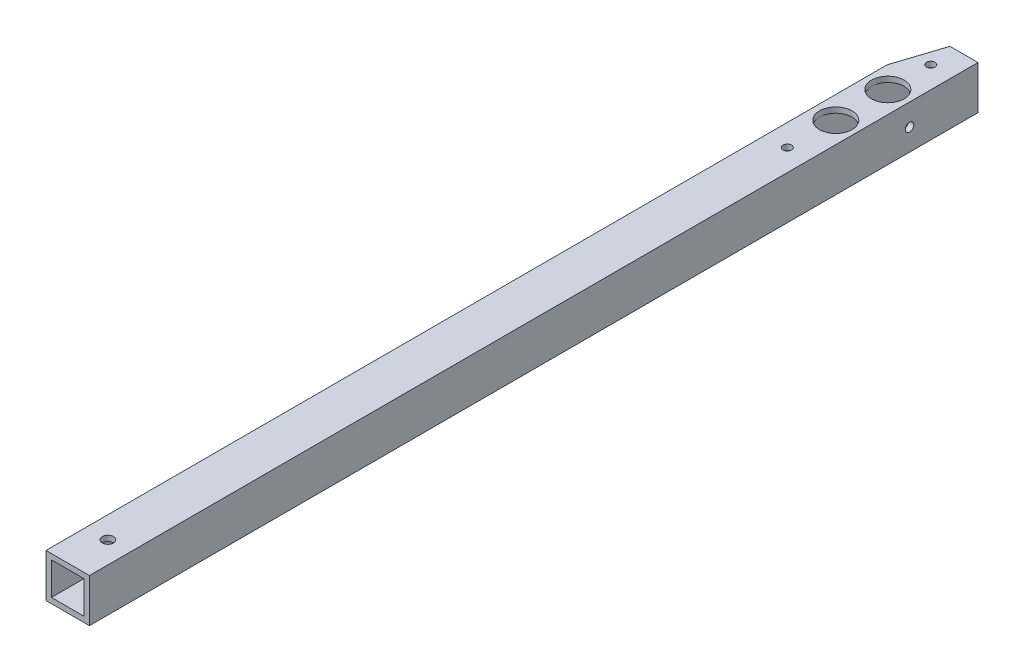
SolidWorks part; units mm, degrees
ref_plane "Front Plane" through (0, 0, 0) normal (0, 0, 1) x (1, 0, 0)
ref_plane "Top Plane" through (0, 0, 0) normal (0, 1, 0) x (1, 0, 0)
ref_plane "Right Plane" through (0, 0, 0) normal (1, 0, 0) x (0, 0, -1)
sketch "Sketch1" plane through (0, 0, 0) normal (0, 0, 1) x (1, 0, 0)
  line L0 (-9.525, 9.525) -> (9.525, 9.525)
  line L2 (-12.7, 12.7) -> (12.7, 12.7)
  line L3 (-12.7, 12.7) -> (-12.7, -12.7)
  line L4 (-12.7, -12.7) -> (12.7, -12.7)
  line L5 (12.7, 12.7) -> (12.7, -12.7)
  line L10 (9.525, 9.525) -> (9.525, -9.525)
  line L11 (-9.525, -9.525) -> (9.525, -9.525)
  line L12 (-9.525, 9.525) -> (-9.525, -9.525)
  point P12 (0, 12.7)
  point P14 (12.7, 0)
  dimension "Wall Thickness" = 3.175
  dimension "Outside Width" = 25.4
  dimension "Outside Height" = 25.4
  dimension "Inside Height" = 19.05
  dimension "Inside Width" = 19.05
sketch "Sketch2" plane through (0, 0, 0) normal (1, 0, 0) x (0, 0, -1)
  line L0 (266.7, 0) -> (-266.7, 0)
  point P4 (0, 0)
  point P7 (-266.7, 0)
  point P10 (266.7, 0)
  dimension "Length" = 533.4
sketch "Sketch3" plane through (0, 0, 0) normal (0, 0, 1) x (1, 0, 0)
  line L21 (12.7, 12.7) -> (-12.7, 12.7)
  line L22 (12.7, -12.7) -> (12.7, 12.7)
  line L23 (-12.7, -12.7) -> (12.7, -12.7)
  line L24 (-12.7, 12.7) -> (-12.7, -12.7)
  line L25 (12.7, 12.7) -> (-12.7, 12.7)
  line L26 (12.7, -12.7) -> (12.7, 12.7)
  line L27 (-12.7, -12.7) -> (12.7, -12.7)
  line L28 (-12.7, 12.7) -> (-12.7, -12.7)
  line L29 (9.525, 9.525) -> (-9.525, 9.525)
  line L30 (9.525, -9.525) -> (9.525, 9.525)
  line L31 (-9.525, -9.525) -> (9.525, -9.525)
  line L32 (-9.525, 9.525) -> (-9.525, -9.525)
  line L33 (9.525, 9.525) -> (-9.525, 9.525)
  line L34 (9.525, -9.525) -> (9.525, 9.525)
  line L35 (-9.525, -9.525) -> (9.525, -9.525)
  line L36 (-9.525, 9.525) -> (-9.525, -9.525)
  dimension "D1" = 0
  dimension "D2" = 0
extrude "Boss-Extrude1" add sketch "Sketch3" along normal up to vertex (266.7 mm away) and the other way up to vertex (266.7 mm away) up to point (0, 0, 266.7) other way up to point (0, 0, -266.7)
sketch "Drawing Reference" plane through (0, 0, 0) normal (1, 0, 0) x (0, 0, -1)
  line L0 (-266.7, 0) -> (266.7, 0) construction
  line L1 (0, -12.7) -> (0, 12.7) construction
  line L2 (-266.7, -12.7) -> (266.7, -12.7) construction
  line L5 (-266.7, 12.7) -> (266.7, 12.7) construction
  point P7 (-248.412, 0)
  point P8 (248.412, 0)
  dimension "D1" = 18.288
sketch "Sketch4" plane through (0, 12.7, 0) normal (0, 1, 0) x (1, 0, 0)
  line L1 (0, 266.7) -> (0, 212.725) construction
  line L7 (-12.7, 225.0135) -> (-12.7, 266.7)
  line L8 (-188.9197, -317.3351) -> (4.6184, 278.3139) construction
  line L10 (-12.7, -266.7) -> (-12.7, 266.7) construction
  line L11 (-12.7, 266.7) -> (12.7, 266.7)
  line L12 (12.7, 266.7) -> (12.7, 252.73)
  line L13 (12.7, -266.7) -> (12.7, 266.7) construction
  line L14 (12.7, 252.73) -> (-3.6943, 252.73)
  line L15 (-3.6943, 252.73) -> (-12.7, 225.0135)
  circle A0 centre (0, 212.725) radius 9.525
  dimension "D1" = 13.97
extrude "Cut-Extrude1" cut sketch "Sketch4" against normal blind 25.4
sketch "Sketch5" plane through (0, 12.7, 0) normal (0, -1, 0) x (1, 0, 0)
  circle A0 centre (0.3539, -181.928) radius 9.525
extrude "Cut-Extrude2" cut sketch "Sketch5" along normal blind 3.175
sketch "Sketch6" plane through (12.7, 0, 0) normal (1, 0, 0) x (0, 0, -1)
  line L0 (252.73, 0) -> (212.725, 0) construction
  line L1 (252.73, -12.7) -> (252.73, 12.7) construction
hole_wizard "#10 Clearance Hole1" positions "Sketch7" profile "Sketch8" hole size "#10" standard "ANSI Inch" end condition through all
sketch "Sketch7" plane through (12.7, 0, 0) normal (1, 0, 0) x (0, 0, -1)
  point P0 (212.725, 0)
sketch "Sketch8" plane through (12.7, 0, -212.725) normal (0, 1, 0) x (0, 0, -1)
  line L0 (0, 0) -> (0, 25.4)
  line L1 (0, 25.4) -> (2.4892, 25.4)
  line L2 (2.4892, 25.4) -> (2.4892, 0)
  line L5 (2.4892, 0) -> (0, 0)
  line L11 (0, -6.35) -> (0, 107.95) construction
  dimension "Thru Hole Dia." = 4.9784
  dimension "Thru Hole Depth" = 25.4
hole_wizard "#10 Clearance Hole2" positions "Sketch9" profile "Sketch10" hole size "#10" standard "ANSI Inch" end condition through all
sketch "Sketch9" plane through (0, -12.7, 0) normal (0, -1, 0) x (-1, 0, 0)
  point P0 (0, 153.96)
  point P3 (0, 237.8065)
sketch "Sketch10" plane through (0, -12.7, -153.96) normal (1, 0, 0) x (0, 0, -1)
  line L0 (0, 0) -> (0, 25.4)
  line L1 (0, 25.4) -> (2.4892, 25.4)
  line L2 (2.4892, 25.4) -> (2.4892, 0)
  line L5 (2.4892, 0) -> (0, 0)
  line L11 (0, -6.35) -> (0, 107.95) construction
  dimension "Thru Hole Dia." = 4.9784
  dimension "Thru Hole Depth" = 25.4
hole_wizard "1/4 Clearance Hole1" positions "Sketch11" profile "Sketch12" hole size "1/4" standard "ANSI Inch" end condition through all
sketch "Sketch11" plane through (0, -12.7, 0) normal (0, -1, 0) x (-1, 0, 0)
  point P0 (0, -243.2272)
sketch "Sketch12" plane through (0, -12.7, 243.2272) normal (1, 0, 0) x (0, 0, -1)
  line L0 (0, 0) -> (0, 25.4)
  line L1 (0, 25.4) -> (3.2639, 25.4)
  line L2 (3.2639, 25.4) -> (3.2639, 0)
  line L5 (3.2639, 0) -> (0, 0)
  line L11 (0, -6.35) -> (0, 107.95) construction
  dimension "Thru Hole Dia." = 6.5278
  dimension "Thru Hole Depth" = 25.4
equation "\"D1@Drawing Reference\"=\"Outside Width@Sketch1\" * 0.72"
